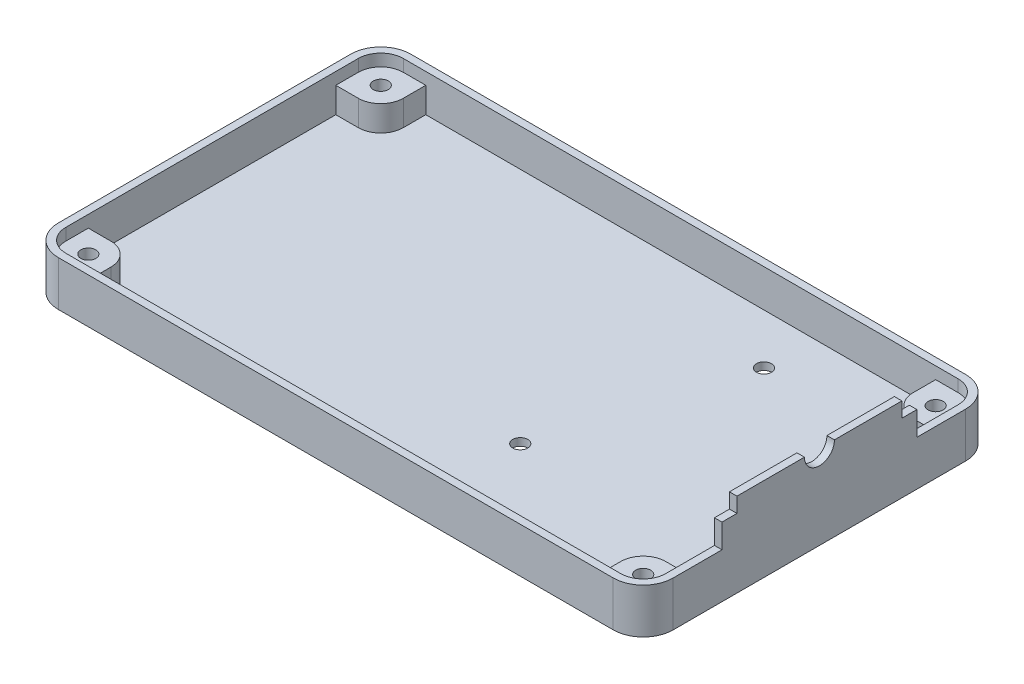
SolidWorks part; units mm, degrees
ref_plane "前视基准面" through (0, 0, 0) normal (0, 0, 1) x (1, 0, 0)
ref_plane "上视基准面" through (0, 0, 0) normal (0, 1, 0) x (1, 0, 0)
ref_plane "右视基准面" through (0, 0, 0) normal (1, 0, 0) x (0, 0, -1)
sketch "草图1" plane through (0, 0, 0) normal (0, 1, 0) x (1, 0, 0)
  line L0 (3, -1) -> (77, -1)
  line L1 (3, 0) -> (77, 0) construction
  line L2 (0, 3) -> (0, 42) construction
  line L3 (3, 45) -> (77, 45) construction
  line L4 (80, 3) -> (80, 42) construction
  line L5 (81, 3) -> (81, 42)
  line L6 (3, 46) -> (77, 46)
  line L7 (-1, 3) -> (-1, 42)
  arc A0 (3, 0) -> (0, 3) centre (3, 3) cw construction
  arc A1 (80, 3) -> (77, 0) centre (77, 3) cw construction
  arc A2 (77, 45) -> (80, 42) centre (77, 42) cw construction
  arc A3 (3, 45) -> (0, 42) centre (3, 42) ccw construction
  arc A4 (81, 3) -> (77, -1) centre (77, 3) cw
  arc A5 (77, 46) -> (81, 42) centre (77, 42) cw
  arc A6 (3, 46) -> (-1, 42) centre (3, 42) ccw
  arc A7 (3, -1) -> (-1, 3) centre (3, 3) cw
  point P7 (0, 0)
  dimension "D1" = 3
  dimension "D2" = 1
extrude "凸台-拉伸1" add sketch "草图1" against normal blind 1
sketch "草图4" plane through (0, 0, 0) normal (0, 1, 0) x (1, 0, 0)
  line L4 (81, 3) -> (81, 42)
  line L5 (77, 46) -> (3, 46)
  line L6 (-1, 42) -> (-1, 3)
  line L7 (3, -1) -> (77, -1)
  line L8 (81, 3) -> (81, 42) construction
  line L9 (77, 46) -> (3, 46) construction
  line L10 (-1, 42) -> (-1, 3) construction
  line L11 (3, -1) -> (77, -1) construction
  circle A0 centre (3, 42) radius 1
  circle A1 centre (3, 3) radius 1
  circle A2 centre (77, 3) radius 1
  circle A3 centre (77, 42) radius 1
  arc A4 (81, 42) -> (77, 46) centre (77, 42) ccw
  arc A5 (3, 46) -> (-1, 42) centre (3, 42) ccw
  arc A6 (-1, 3) -> (3, -1) centre (3, 3) ccw
  arc A7 (77, -1) -> (81, 3) centre (77, 3) ccw
  arc A8 (81, 42) -> (77, 46) centre (77, 42) ccw construction
  arc A9 (3, 46) -> (-1, 42) centre (3, 42) ccw construction
  arc A10 (-1, 3) -> (3, -1) centre (3, 3) ccw construction
  arc A11 (77, -1) -> (81, 3) centre (77, 3) ccw construction
  dimension "D1" = 0
sketch "草图5" plane through (0, 0, 0) normal (0, 1, 0) x (1, 0, 0)
  line L4 (81, 3) -> (81, 42)
  line L5 (77, 46) -> (3, 46)
  line L6 (-1, 42) -> (-1, 3)
  line L7 (3, -1) -> (77, -1)
  line L8 (81, 3) -> (81, 42) construction
  line L9 (77, 46) -> (3, 46) construction
  line L10 (-1, 42) -> (-1, 3) construction
  line L11 (3, -1) -> (77, -1) construction
  line L17 (77, 6) -> (80, 6)
  line L18 (80, 6) -> (80, 3)
  line L19 (74, 3) -> (74, 0)
  line L20 (74, 0) -> (77, 0)
  line L21 (77, 45) -> (74, 45)
  line L22 (74, 45) -> (74, 42)
  line L23 (77, 39) -> (80, 39)
  line L24 (80, 39) -> (80, 42)
  line L32 (0, 42) -> (0, 39)
  line L33 (0, 39) -> (3, 39)
  line L34 (3, 45) -> (6, 45)
  line L35 (6, 45) -> (6, 42)
  line L36 (3, 6) -> (0, 6)
  line L37 (0, 6) -> (0, 3)
  line L38 (6, 3) -> (6, 0)
  line L39 (6, 0) -> (3, 0)
  arc A2 (77, 0) -> (80, 3) centre (77, 3) ccw
  arc A3 (74, 42) -> (77, 39) centre (77, 42) ccw
  arc A4 (81, 42) -> (77, 46) centre (77, 42) ccw
  arc A5 (3, 46) -> (-1, 42) centre (3, 42) ccw
  arc A6 (-1, 3) -> (3, -1) centre (3, 3) ccw
  arc A7 (77, -1) -> (81, 3) centre (77, 3) ccw
  arc A8 (81, 42) -> (77, 46) centre (77, 42) ccw construction
  arc A9 (3, 46) -> (-1, 42) centre (3, 42) ccw construction
  arc A10 (-1, 3) -> (3, -1) centre (3, 3) ccw construction
  arc A11 (77, -1) -> (81, 3) centre (77, 3) ccw construction
  arc A14 (77, 6) -> (74, 3) centre (77, 3) ccw
  arc A15 (80, 42) -> (77, 45) centre (77, 42) ccw
  arc A16 (3, 45) -> (0, 42) centre (3, 42) ccw
  arc A21 (0, 3) -> (3, 0) centre (3, 3) ccw
  arc A22 (6, 3) -> (3, 6) centre (3, 3) ccw
  arc A23 (3, 39) -> (6, 42) centre (3, 42) ccw
  dimension "D1" = 0
sketch "草图6" plane through (0, 0, 0) normal (0, 1, 0) x (1, 0, 0)
  line L0 (80, 3) -> (80, 42)
  line L1 (77, 45) -> (3, 45)
  line L2 (0, 42) -> (0, 3)
  line L3 (3, 0) -> (77, 0)
  line L4 (81, 3) -> (81, 42)
  line L5 (77, 46) -> (3, 46)
  line L6 (-1, 42) -> (-1, 3)
  line L7 (3, -1) -> (77, -1)
  line L8 (81, 3) -> (81, 42) construction
  line L9 (77, 46) -> (3, 46) construction
  line L10 (-1, 42) -> (-1, 3) construction
  line L11 (3, -1) -> (77, -1) construction
  arc A0 (80, 42) -> (77, 45) centre (77, 42) ccw
  arc A1 (3, 45) -> (0, 42) centre (3, 42) ccw
  arc A2 (0, 3) -> (3, 0) centre (3, 3) ccw
  arc A3 (77, 0) -> (80, 3) centre (77, 3) ccw
  arc A4 (81, 42) -> (77, 46) centre (77, 42) ccw
  arc A5 (3, 46) -> (-1, 42) centre (3, 42) ccw
  arc A6 (-1, 3) -> (3, -1) centre (3, 3) ccw
  arc A7 (77, -1) -> (81, 3) centre (77, 3) ccw
  arc A8 (81, 42) -> (77, 46) centre (77, 42) ccw construction
  arc A9 (3, 46) -> (-1, 42) centre (3, 42) ccw construction
  arc A10 (-1, 3) -> (3, -1) centre (3, 3) ccw construction
  arc A11 (77, -1) -> (81, 3) centre (77, 3) ccw construction
  dimension "D1" = 0
  dimension "D2" = 1
extrude "凸台-拉伸2" add sketch "草图1<3>" along normal blind 5
sketch "草图1<3>" plane through (0, 0, 0) normal (0, 1, 0) x (1, 0, 0) same geometry as "草图1"
extrude "切除-拉伸2" cut sketch "草图6" along normal blind 5
extrude "凸台-拉伸3" add sketch "草图5" along normal blind 3.4
extrude "切除-拉伸3" cut sketch "草图4" against normal through all both and the other way through all
sketch "草图7" plane through (0, 0, 0) normal (0, 1, 0) x (1, 0, 0)
  line L1 (0, 45) -> (50.3, 45) construction
  line L2 (0, 45) -> (0, 13.3) construction
  line L3 (0, 13.3) -> (50.3, 13.3) construction
  line L4 (0, 42) -> (0, 3)
  line L5 (3, 0) -> (77, 0)
  line L6 (80, 3) -> (80, 42)
  line L7 (77, 45) -> (3, 45)
  line L8 (0, 42) -> (0, 3) construction
  line L9 (3, 0) -> (77, 0) construction
  line L10 (80, 3) -> (80, 42) construction
  line L11 (77, 45) -> (3, 45) construction
  line L12 (50.3, 45) -> (50.3, 13.3) construction
  line L13 (0, 45) -> (57.8, 45) construction
  line L14 (0, 45) -> (0, 38.3) construction
  line L15 (0, 38.3) -> (57.8, 38.3) construction
  line L16 (57.8, 45) -> (57.8, 38.3) construction
  circle A0 centre (50.3, 13.3) radius 1
  circle A1 centre (57.8, 38.3) radius 1
  arc A4 (0, 3) -> (3, 0) centre (3, 3) ccw
  arc A5 (77, 0) -> (80, 3) centre (77, 3) ccw
  arc A6 (80, 42) -> (77, 45) centre (77, 42) ccw
  arc A7 (3, 45) -> (0, 42) centre (3, 42) ccw
  arc A8 (0, 3) -> (3, 0) centre (3, 3) ccw construction
  arc A9 (77, 0) -> (80, 3) centre (77, 3) ccw construction
  arc A10 (80, 42) -> (77, 45) centre (77, 42) ccw construction
  arc A11 (3, 45) -> (0, 42) centre (3, 42) ccw construction
  dimension "D1" = 0
extrude "切除-拉伸8" cut sketch "草图7" against normal through all
sketch "草图8" plane through (0, -1, 0) normal (0, -1, 0) x (1, 0, 0)
  circle A0 centre (3, -3) radius 2.6
  circle A1 centre (77, -3) radius 2.6
  circle A2 centre (3, -42) radius 2.6
  circle A3 centre (77, -42) radius 2.6
extrude "切除-拉伸9" cut sketch "草图8" against normal blind 2
sketch "草图9" plane through (0, 5, 0) normal (0, 1, 0) x (1, 0, 0)
  line L5 (81, 22.5) -> (81, 35.5) construction
  line L6 (81, 3) -> (81, 42) construction
  line L7 (80, 22.5) -> (80, 9.5) construction
  line L8 (80, 3) -> (80, 42) construction
  line L14 (81, 35.5) -> (80, 35.5)
  line L15 (81, 35.5) -> (81, 9.5)
  line L16 (81, 9.5) -> (80, 9.5)
  line L17 (80, 35.5) -> (80, 9.5)
extrude "凸台-拉伸4" add sketch "草图9" along normal blind 5.2
sketch "草图10" plane through (81, 0, 0) normal (1, 0, 0) x (0, 0, -1)
  line L0 (9.5, 10.2) -> (35.5, 10.2) construction
  line L1 (22.5, 10.2) -> (34.5, 10.2) construction
  line L2 (22.5, 10.2) -> (10.5, 10.2) construction
  line L7 (35.5, 10.2) -> (35.5, 5) construction
  line L8 (9.5, 12.2) -> (11.5, 12.2)
  line L9 (9.5, 12.2) -> (9.5, 8.2)
  line L14 (9.5, 8.2) -> (11.5, 8.2)
  line L15 (11.5, 12.2) -> (11.5, 8.2)
  line L16 (9.5, 12.2) -> (11.5, 8.2) construction
  line L17 (9.5, 8.2) -> (11.5, 12.2) construction
  line L18 (33.5, 12.2) -> (35.5, 12.2)
  line L19 (33.5, 12.2) -> (33.5, 8.2)
  line L20 (33.5, 8.2) -> (35.5, 8.2)
  line L21 (35.5, 12.2) -> (35.5, 8.2)
  line L22 (33.5, 12.2) -> (35.5, 8.2) construction
  line L23 (33.5, 8.2) -> (35.5, 12.2) construction
  circle A0 centre (22.5, 10.2) radius 2
extrude "切除-拉伸11" cut sketch "草图10" against normal up to next
